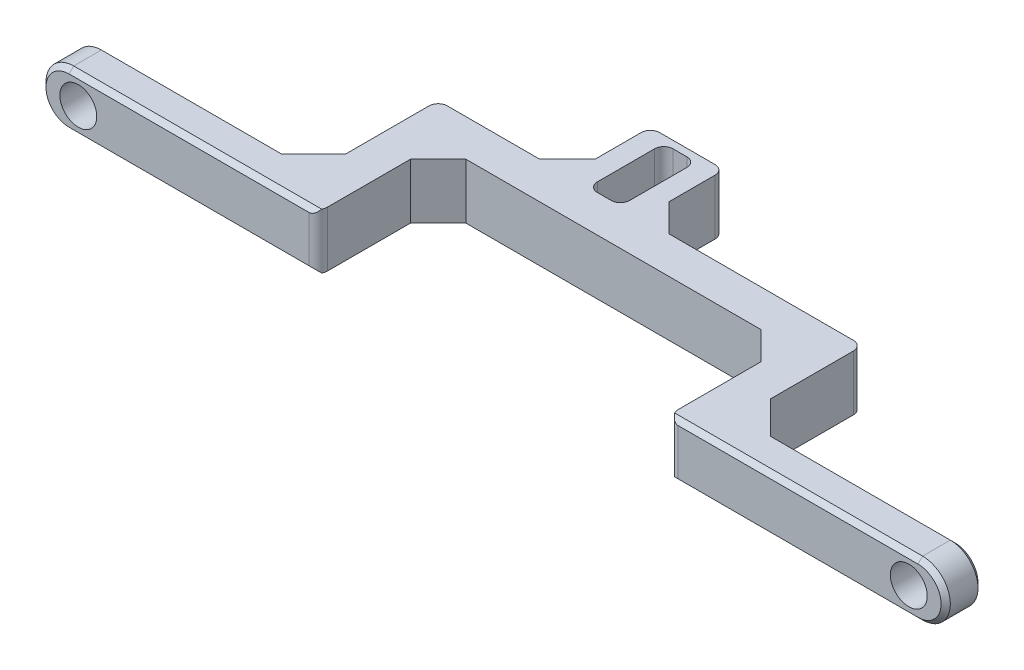
SolidWorks part; units mm, degrees
ref_plane "Alzado" through (0, 0, 0) normal (0, 0, 1) x (1, 0, 0)
ref_plane "Planta" through (0, 0, 0) normal (0, 1, 0) x (1, 0, 0)
ref_plane "Vista lateral" through (0, 0, 0) normal (1, 0, 0) x (0, 0, -1)
sketch "Croquis1" plane through (0, 0, 0) normal (0, 0, 1) x (1, 0, 0)
  line L0 (0, 0) -> (90, 0) construction
  circle A0 centre (0, 0) radius 3
  circle A1 centre (90, 0) radius 3
  dimension "D1" = 6
  dimension "D2" = 6
  dimension "D3" = 90
extrude "Saliente-Extruir1" add sketch "Croquis1" along normal blind 4
sketch "Croquis2" plane through (0, 0, 0) normal (0, 0, 1) x (1, 0, 0)
  line L1 (0, -3) -> (90, -3)
  line L2 (0, -3) -> (0, 3)
  line L3 (0, 3) -> (90, 3)
  line L4 (90, -3) -> (90, 3)
  circle A0 centre (0, 0) radius 3 construction
  circle A1 centre (90, 0) radius 3 construction
  dimension "D1" = 90
  dimension "D2" = 6
extrude "Saliente-Extruir2" add sketch "Croquis2" along normal blind 4
sketch "Croquis4" plane through (0, 3, 0) normal (0, 1, 0) x (1, 0, 0)
  line L1 (22, 13) -> (68, 13)
  line L2 (22, 13) -> (22, 0)
  line L3 (22, 0) -> (68, 0)
  line L4 (68, 13) -> (68, 0)
  line L5 (90, 0) -> (0, 0) construction
  line L7 (90, -4) -> (0, -4) construction
  point P5 (45, 0)
  point P6 (45, 0)
  dimension "D1" = 22
  dimension "D2" = 17
extrude "Saliente-Extruir3" add sketch "Croquis4" against normal blind 6
sketch "Croquis5" plane through (0, 3, 0) normal (0, 1, 0) x (1, 0, 0)
  line L0 (90, -4) -> (0, -4) construction
  line L1 (26, -4) -> (64, -4)
  line L2 (26, -4) -> (26, 9)
  line L3 (26, 9) -> (64, 9)
  line L4 (64, -4) -> (64, 9)
  line L5 (68, 13) -> (22, 13) construction
  line L6 (22, 13) -> (22, 0) construction
  line L7 (68, 0) -> (68, 13) construction
  point P12 (68, 6.5)
  dimension "D1" = 4
  dimension "D2" = 4
  dimension "D3" = 4
extrude "Cortar-Extruir1" cut sketch "Croquis5" against normal through all
sketch "Croquis6" plane through (0, 0, 0) normal (0, 1, 0) x (1, 0, 0)
  line L0 (68, 13) -> (22, 13) construction
  line L2 (36, 22) -> (44, 22)
  line L3 (36, 22) -> (36, 13)
  line L4 (36, 13) -> (44, 13)
  line L5 (44, 22) -> (44, 13)
  point P0 (45, 13)
  point P1 (40, 13)
  dimension "D1" = 5
  dimension "D2" = 9
  dimension "D3" = 8
extrude "Saliente-Extruir4" add sketch "Croquis6" against normal mid plane 6
sketch "Croquis7" plane through (0, 3, 0) normal (0, 1, 0) x (1, 0, 0)
  line L0 (40, 21.2) -> (40, 22) construction
  line L1 (38.25, 21.2) -> (41.75, 21.2)
  line L2 (38.25, 21.2) -> (38.25, 13)
  line L3 (38.25, 13) -> (41.75, 13)
  line L4 (41.75, 21.2) -> (41.75, 13)
  line L5 (44, 22) -> (36, 22) construction
  line L6 (36, 13) -> (22, 13) construction
  dimension "D1" = 0.8
  dimension "D2" = 3.5
extrude "Cortar-Extruir2" cut sketch "Croquis7" against normal through all
chamfer "Chaflán1" distance 3 angle 45 6 edges at (22, 0, 0) (68, 0, 0) (26, 0, -9) (64, 0, -9) (36, 0, -13) (44, 0, -13)
fillet "Redondeo1" radius 1 10 edges at (41.75, 0, -13) (38.25, 0, -13) (38.25, 0, -21.2) (41.75, 0, -21.2) (68, 0, -13) (64, 0, 4) (26, 0, 4) (22, 0, -13) (36, 0, -22) (44, 0, -22)
sketch "Croquis8" plane through (0, 0, 4) normal (0, 0, 1) x (1, 0, 0)
  circle A0 centre (0, 0) radius 1.75
  circle A1 centre (90, 0) radius 1.75
  dimension "D1" = 3.5
  dimension "D2" = 3.5
extrude "Cortar-Extruir3" cut sketch "Croquis8" against normal through all
ref_plane "Plano1" through (45, 0, 0) normal (1, 0, 0) x (0, 0, -1)
sketch "Croquis9" plane through (0, 0, 4) normal (0, 0, 1) x (1, 0, 0)
  line L0 (-1, 3) -> (0, 3)
  line L1 (-1, -3) -> (0, -3)
  line L2 (0, 2.5) -> (0, 3)
  line L3 (0, -3) -> (0, -2.5)
  arc A0 (-1, 3) -> (-1, -3) centre (-1, 0) ccw
  arc A1 (0, 2.5) -> (0, -2.5) centre (0, 0) ccw
  dimension "D1" = 1
  dimension "D2" = 5
extrude "Saliente-Extruir5" add sketch "Croquis9" against normal blind 4
mirror "Simetría1" about plane through (45, 0, 0) normal (1, 0, 0) of "Saliente-Extruir5"
sketch "Croquis10" plane through (0, 0, 0) normal (0, 0, -1) x (-1, 0, 0)
  circle A3 centre (0, 0) radius 2
  circle A6 centre (-90, 0) radius 2
  dimension "D1" = 4
extrude "Cortar-Extruir4" cut sketch "Croquis10" against normal through all
chamfer "Chaflán2" distance 0.5 angle 45 4 edges at (94, 0, 4) (94, 0, 0) (-4, 0, 4) (-4, 0, 0)
